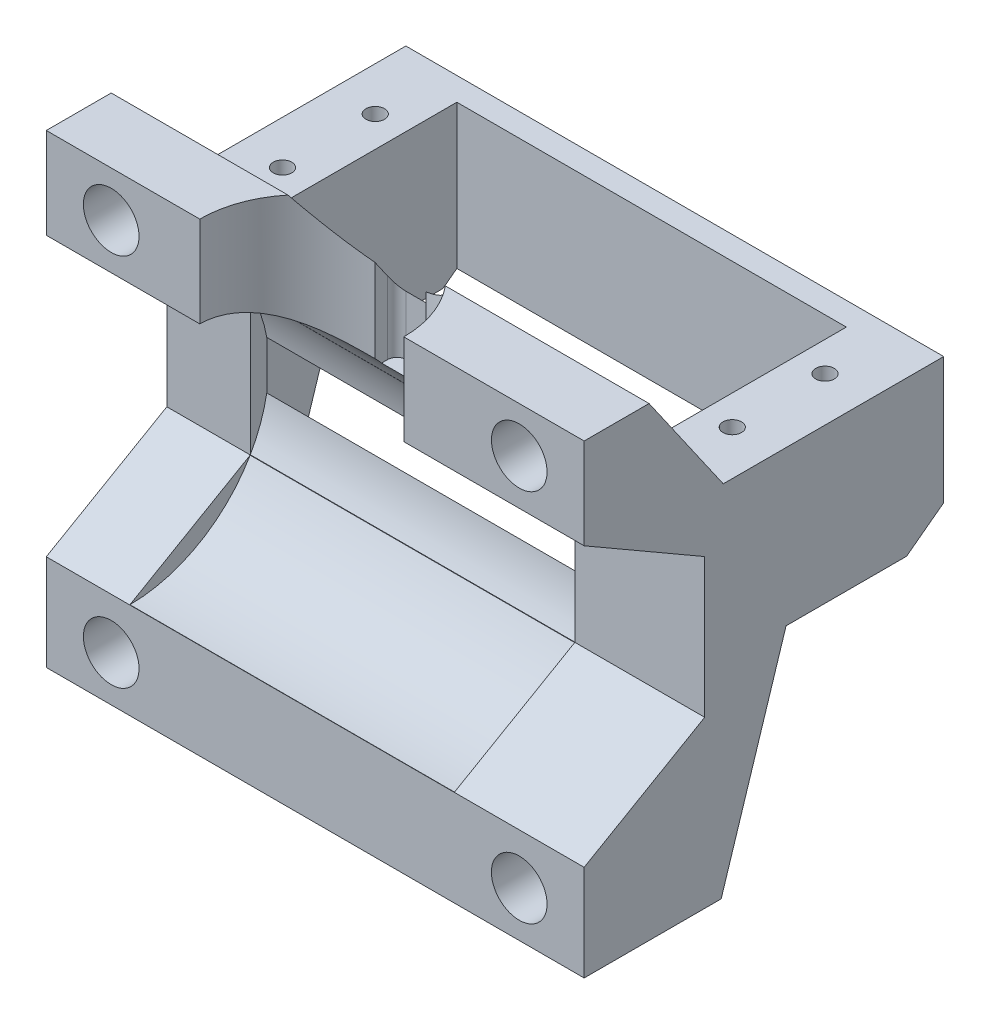
SolidWorks part; units mm, degrees
ref_plane "Front Plane" through (0, 0, 0) normal (0, 0, 1) x (1, 0, 0)
ref_plane "Top Plane" through (0, 0, 0) normal (0, 1, 0) x (1, 0, 0)
ref_plane "Right Plane" through (0, 0, 0) normal (1, 0, 0) x (0, 0, -1)
ref_plane "Plane1" through (0, -30, 0) normal (0, 1, 0) x (1, 0, 0)
sketch "Sketch1" plane through (0, -30, 0) normal (0, 1, 0) x (1, 0, 0)
  line L0 (-4.2598, -25.7738) -> (4.15, -25.7738) construction
  line L1 (29, -25.7738) -> (-29, -25.7738)
  line L2 (29, -25.7738) -> (29, 13)
  line L3 (29, 13) -> (-29, 13)
  line L4 (-29, -25.7738) -> (-29, 13)
  line L5 (29, -25.7738) -> (-29, 13) construction
  line L6 (29, 13) -> (-29, -25.7738) construction
  line L8 (27, 3.8) -> (27, -3.8) construction
  line L9 (-8.46, 10) -> (19.75, 10) construction
  line L10 (-27, -3.8) -> (-27, 3.8) construction
  line L12 (21, 10.5) -> (-21, 10.5)
  line L13 (21, 10.5) -> (21, -11)
  line L14 (21, -11) -> (-21, -11)
  line L15 (-21, 10.5) -> (-21, -11)
  point P0 (0, -6.3869)
  point P9 (-0.0549, -25.7738)
  dimension "D1" = 2
  dimension "D2" = 2.5
  dimension "D3" = 2
  dimension "D4" = 3
  dimension "D5" = 8
  dimension "D6" = 8
  dimension "D7" = 21.5
extrude "Boss-Extrude2" add sketch "Sketch1" along normal up to surface (38.65 mm away)
sketch "Sketch6" plane through (29, 0, 0) normal (1, 0, 0) x (0, 0, -1)
  line L0 (-11, -30) -> (-4, -8)
  line L1 (-25.7738, -30) -> (13, -30) construction
  line L2 (-4, -8) -> (9, -8)
  line L3 (9, -8) -> (13, -5)
  line L4 (13, 8.65) -> (13, -30) construction
  line L5 (13, -5) -> (13, -30)
  line L6 (13, -30) -> (-11, -30)
  dimension "D1" = 24
  dimension "D2" = 17
  dimension "D3" = 22
  dimension "D4" = 3
  dimension "D5" = 4
extrude "Cut-Extrude3" cut sketch "Sketch6" against normal through all
sketch "Sketch7" plane through (0, -8, 0) normal (0, -1, 0) x (1, 0, 0)
  line L0 (-21, -9) -> (-21, 4) construction
  line L1 (-21, -9) -> (-29, -9)
  line L2 (-21, -9) -> (-21, 4)
  line L3 (-21, 4) -> (-29, 4)
  line L4 (-29, -9) -> (-29, 4)
  line L5 (-29, 4) -> (-29, 11) construction
  line L6 (-29, -9) -> (-21, -9) construction
  line L7 (-29, 4) -> (-21, 4) construction
extrude "Cut-Extrude4" [suppressed] cut sketch "Sketch7" against normal blind 8
sketch "Sketch8" plane through (-29, 0, 0) normal (-1, 0, 0) x (0, 0, 1)
  line L0 (25.7738, 8.65) -> (25.7738, -30) construction
  line L1 (25.7738, 10.3611) -> (12.7738, 2.8556)
  line L2 (12.7738, 2.8556) -> (12.7738, -12.1556)
  line L3 (12.7738, -12.1556) -> (25.7738, -19.6611)
  line L4 (25.7738, -19.6611) -> (38.7738, -12.1556)
  line L5 (38.7738, -12.1556) -> (38.7738, 2.8556)
  line L6 (38.7738, 2.8556) -> (25.7738, 10.3611)
  circle A0 centre (25.7738, -4.65) radius 13 construction
  dimension "D1" = 13
sketch "Sketch9" plane through (-29, 0, 0) normal (-1, 0, 0) x (0, 0, 1)
  line L0 (10.7738, 8.65) -> (18.7738, 20.15)
  line L1 (25.7738, 8.65) -> (-13, 8.65) construction
  line L2 (18.7738, 20.15) -> (25.7738, 20.15)
  line L3 (25.7738, 20.15) -> (25.7738, 8.65)
  line L4 (10.7738, 8.65) -> (25.7738, 8.65)
  dimension "D1" = 7
  dimension "D2" = 11.5
  dimension "D3" = 15
extrude "Boss-Extrude3" add sketch "Sketch9" against normal up to surface (58 mm away) up to face at (29, -9.1, 4.5068)
extrude "Cut-Extrude5" cut sketch "Sketch8" against normal through all
sketch "Sketch10" plane through (0, 20.15, 0) normal (0, 1, 0) x (1, 0, 0)
  line L0 (29, -25.7738) -> (-29, -25.7738) construction
  line L1 (-4.2, -25.7738) -> (1.3, -25.7738)
  line L2 (-4.2, -25.7738) -> (-4.2, -12.7738)
  line L3 (-4.2, -12.7738) -> (1.3, -12.7738)
  line L4 (1.3, -25.7738) -> (1.3, -12.7738)
  circle A0 centre (-1.45, -25.7738) radius 11
  arc A1 (-7.95, -25.7738) -> (5.05, -25.7738) centre (-1.45, -25.7738) ccw construction
  point P11 (-1.45, -12.7738)
  line M7 (29, -18.7738) -> (-29, -18.7738)
  line M9 (-29, -25.7738) -> (29, -25.7738)
  dimension "D1" = 22
  dimension "D2" = 5.5
  dimension "D3" = 13
extrude "Cut-Extrude6" cut sketch "Sketch10" against normal blind 15 contours A0 L4 L3 L2 | A0 L4 M9 M7 | A0 L4 M7 | L4 A0 L2 M7 | A0 L2 M7 M9 | L4 L2 M9 M7 | L2 A0 M7 region at (-1.45, 20.15, 22.2738) region at (-7.9633, 20.15, 22.4652) region at (5.0633, 20.15, 22.4652) region at (-6.3152, 20.15, 17.4069) region at (-1.45, 20.15, 16.8303) region at (3.4152, 20.15, 17.4069) region at (-1.45, 20.15, 13.8342)
fillet "Fillet1" radius 1 2 edges at (1.3, 8.3375, 12.7738) (-4.2, 8.3375, 12.7738)
sketch "Sketch11" plane through (0, 0, 0) normal (1, 0, 0) x (0, 0, -1)
  circle A0 centre (-25.7738, -4.65) radius 15
  dimension "D1" = 30
extrude "Cut-Extrude7" cut sketch "Sketch11" against normal blind 20 and the other way blind 15 contours A0
sketch "Sketch12" plane through (0, 0, 25.7738) normal (0, 0, 1) x (1, 0, 0)
  line L0 (-29, -4.925) -> (29, -4.925) construction
  line L1 (-29, 20.15) -> (-29, 10.3611) construction
  line L2 (29, 20.15) -> (29, 10.3611) construction
  line L3 (-29, -30) -> (29, -30) construction
  line L4 (29, 20.15) -> (9.55, 20.15) construction
  circle A0 centre (-22, 15.2556) radius 3
  circle A1 centre (22, 15.2556) radius 3
  circle A2 centre (22, -25.1056) radius 3
  circle A3 centre (-22, -25.1056) radius 3
  point P14 (-29, 15.2556)
  dimension "D1" = 6
  dimension "D2" = 7
  dimension "D3" = 7
extrude "Cut-Extrude8" cut sketch "Sketch12" against normal blind 20
sketch "Sketch13" plane through (0, 0, 0) normal (0, 0, 1) x (1, 0, 0)
  line L0 (-29, -4.925) -> (29, -4.925) construction
  line L1 (29, 8.65) -> (29, -5) construction
  line L2 (-29, 8.65) -> (-29, -5) construction
  line L3 (29, 20.15) -> (7.0353, 20.15) construction
  line L4 (-21, -30) -> (21, -30) construction
  circle A0 centre (22, 15.2556) radius 4
  circle A1 centre (-22, 15.2556) radius 4
  circle A2 centre (22, -25.1056) radius 4
  circle A3 centre (-22, -25.1056) radius 4
  dimension "D1" = 8
extrude "Cut-Extrude9" cut sketch "Sketch13" along normal blind 20
sketch "Sketch15" plane through (0, 8.65, 0) normal (0, 1, 0) x (1, 0, 0)
  line L0 (29, 13) -> (29, -10.7738) construction
  line L1 (-29, 0) -> (29, 0) construction
  line L2 (-29, -10.7738) -> (-29, 13) construction
  circle A0 centre (-24.3, 5) radius 1
  circle A1 centre (-24.3, -5) radius 1
  circle A2 centre (24.2, 5) radius 1
  circle A3 centre (24.2, -5) radius 1
  dimension "D1" = 2
  dimension "D2" = 2
  dimension "D3" = 48.5
extrude "Cut-Extrude10" cut sketch "Sketch15" against normal blind 10
